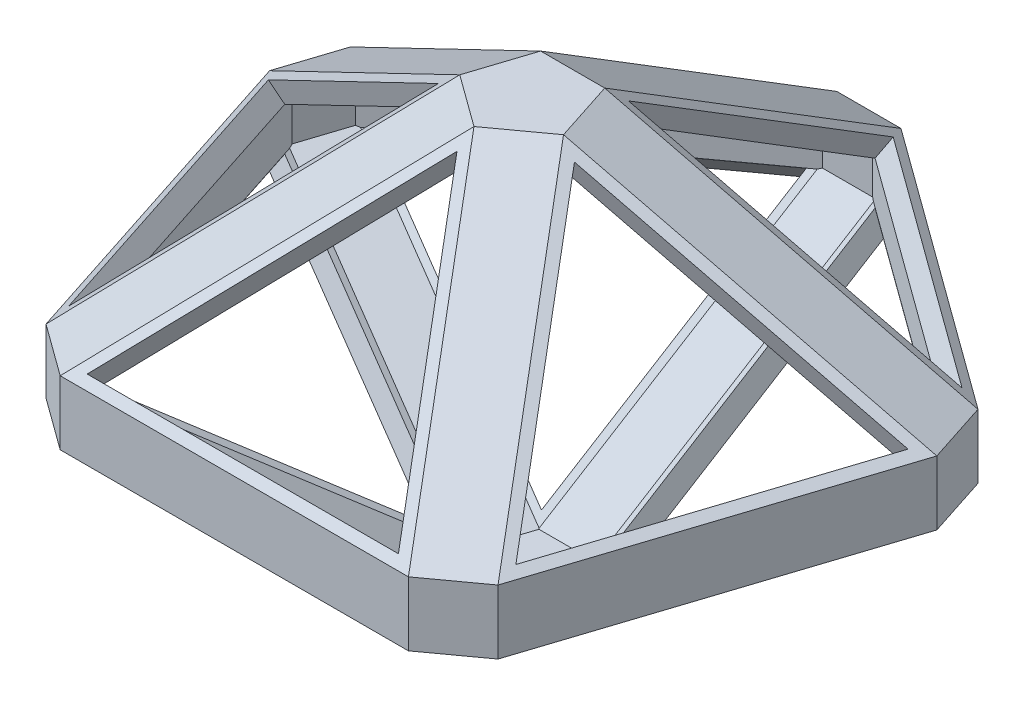
SolidWorks part; units mm, degrees
note: '?' marks a value the reader was unsure of. The reader was unsure of these and kept them because the rebuilt part matched: shared geometry of "草图2<2>".
ref_plane "前视基准面" through (0, 0, 0) normal (0, 0, 1) x (1, 0, 0)
ref_plane "上视基准面" through (0, 0, 0) normal (0, 1, 0) x (1, 0, 0)
ref_plane "右视基准面" through (0, 0, 0) normal (1, 0, 0) x (0, 0, -1)
other "Configuration Table"
sketch "草图1" plane through (0, 0, 0) normal (0, 1, 0) x (1, 0, 0)
  line L0 (-6, 63.6928) -> (6, 63.6928)
  line L1 (40, -55.0553) -> (64.7214, 21.0292)
  line L2 (64.7214, 21.0292) -> (0, 68.0521)
  line L3 (0, 68.0521) -> (-64.7214, 21.0292)
  line L4 (-64.7214, 21.0292) -> (-40, -55.0553)
  line L5 (-40, -55.0553) -> (40, -55.0553)
  line L6 (0, 0) -> (0, 74.3193) construction
  line L7 (0, 0) -> (70.6818, 22.9659) construction
  line L8 (58.7214, 25.3885) -> (62.4296, 13.9758)
  line L9 (0, 0) -> (43.6838, -60.1256) construction
  line L10 (42.2918, -48.0019) -> (32.5836, -55.0553)
  line L11 (0, 0) -> (-43.6838, -60.1256) construction
  line L12 (-32.5836, -55.0553) -> (-42.2918, -48.0019)
  line L13 (0, 0) -> (-70.6818, 22.9659) construction
  line L14 (-62.4296, 13.9758) -> (-58.7214, 25.3885)
  circle A0 centre (0, 0) radius 55.0553 construction
  point P26 (0, 0)
  dimension "D1" = 80
  dimension "D2" = 12
  dimension "D3" = 5
extrude "凸台-拉伸1" add sketch "草图1" along normal blind 6 contours L14 L4 L12 L5 L10 L1 L8 L2 L0 L3
sketch "草图2" plane through (0, 6, 0) normal (0, 1, 0) x (1, 0, 0)
  line L1 (-6, 8.2583) -> (-9.7082, -3.1544)
  line L2 (-9.7082, -3.1544) -> (0, -10.2078)
  line L3 (0, -10.2078) -> (9.7082, -3.1544)
  line L4 (9.7082, -3.1544) -> (6, 8.2583)
  line L5 (6, 8.2583) -> (-6, 8.2583)
  circle A0 centre (0, 0) radius 8.2583 construction
  dimension "D1" = 12
extrude "凸台-拉伸2" add sketch "草图2" along normal blind 50
sketch3d "3D草图1"
  line L0 (42.2918, 6, 48.0019) -> (9.7082, 40.2604, 3.1544)
  line L1 (9.7082, 56, 3.1544) -> (9.7082, 6, 3.1544) construction
  line L2 (9.7082, 40.2604, 3.1544) -> (62.4296, 6, -13.9758)
  line L3 (62.4296, 6, -13.9758) -> (42.2918, 6, 48.0019)
ref_plane "基准面1" through (22.0489, 30.3478, 7.1641) normal (-0.5774, -0.7947, -0.1876) x (-0.8165, 0.5619, 0.1326)
sketch "草图3" plane through (22.0489, 30.3478, 7.1641) normal (-0.5774, -0.7947, -0.1876) x (-0.8165, 0.5619, 0.1326)
  line L0 (-49.456, 14.9805) -> (-24.7923, -45.3392) construction
  line L1 (15.1143, 6.1799) -> (-49.456, 14.9805) construction
  line L2 (-24.7923, -45.3392) -> (15.1143, 6.1799) construction
  line L3 (-49.456, 14.9805) -> (-24.7923, -45.3392)
  line L4 (15.1143, 6.1799) -> (-49.456, 14.9805)
  line L5 (-24.7923, -45.3392) -> (15.1143, 6.1799)
extrude "凸台-拉伸3" add sketch "草图3" along normal up to next
ref_axis "基准轴1" through (0, 59.1929, 0) along (0, -1, 0)?
sketch3d "3D草图2"
  line L0 (62.4296, 6, -13.9758) -> (9.7082, 40.2604, 3.1544)
  line L1 (9.7082, 40.2604, 3.1544) -> (6, 40.2604, -8.2583)
  line L2 (6, 56, -8.2583) -> (6, 6, -8.2583) construction
  line L3 (6, 40.2604, -8.2583) -> (58.7214, 6, -25.3885)
  line L4 (58.7214, 6, -25.3885) -> (62.4296, 6, -13.9758)
  point P9 (0, 0, 0)
ref_plane "基准面2" through (19.2946, 32.8259, -6.2692) normal (0.5, 0.8507, -0.1625) x (0.866, -0.4911, 0.0938)
sketch "草图5" plane through (19.2946, 32.8259, -6.2692) normal (0.5, 0.8507, -0.1625) x (0.866, -0.4911, 0.0938)
  line L0 (-11.0694, -10.6509) -> (49.808, 12.6022) construction
  line L1 (45.5261, 23.8122) -> (49.808, 12.6022) construction
  line L2 (-15.3513, 0.5591) -> (45.5261, 23.8122) construction
  line L3 (-11.0694, -10.6509) -> (-15.3513, 0.5591) construction
  line L4 (-11.0694, -10.6509) -> (49.808, 12.6022)
  line L5 (45.5261, 23.8122) -> (49.808, 12.6022)
  line L6 (-15.3513, 0.5591) -> (45.5261, 23.8122)
  line L7 (-11.0694, -10.6509) -> (-15.3513, 0.5591)
extrude "凸台-拉伸4" add sketch "草图5" against normal up to next
pattern_circular "阵列(圆周)1" count 5 over 360 about axis through (0, 0, 0) along (0, 1, 0) of "凸台-拉伸4", "凸台-拉伸3"
extrude "切除-拉伸2" cut sketch "草图2<2>" against normal up to vertex from vertex
sketch "草图2<2>" plane through (0, 6, 0) normal (0, 1, 0) x (1, 0, 0) same geometry as "草图2"
mirror "镜向1" about plane through (0, 0, 0) normal (0, 1, 0) of bodies 111
shell "抽壳2" thickness 4
sketch "草图6" plane through (22.0489, 30.3478, 7.1641) normal (0.5774, 0.7947, 0.1876) x (0.8165, -0.5619, -0.1326)
  line L9 (-11.4118, 4.6661) -> (24.2521, -41.3759)
  line L10 (24.2521, -41.3759) -> (46.2937, 12.531)
  line L11 (46.2937, 12.531) -> (-11.4118, 4.6661)
  line L12 (-11.4118, 4.6661) -> (24.2521, -41.3759)
  line L13 (24.2521, -41.3759) -> (46.2937, 12.531)
  line L14 (46.2937, 12.531) -> (-11.4118, 4.6661)
  dimension "D1" = 2
extrude "切除-拉伸3" cut sketch "草图6" against normal blind 4
pattern_circular "阵列(圆周)2" count 5 over 360 about axis through (0, 0, 0) along (0, 1, 0) of "切除-拉伸3"
mirror "镜向2" about plane through (0, 0, 0) normal (0, 1, 0) of "阵列(圆周)2", "切除-拉伸3"
